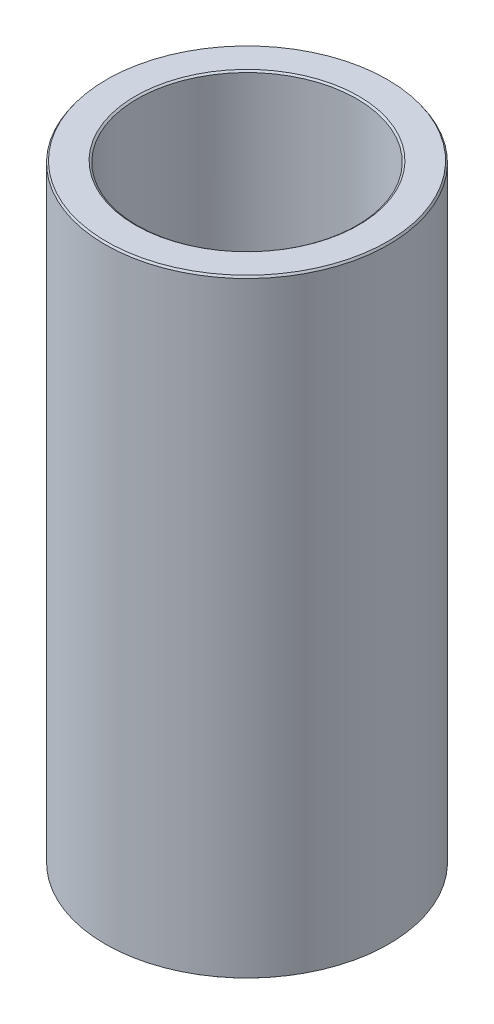
SolidWorks part; units mm, degrees
ref_plane "Front Plane" through (0, 0, 0) normal (0, 0, 1) x (1, 0, 0)
ref_plane "Top Plane" through (0, 0, 0) normal (0, 1, 0) x (1, 0, 0)
ref_plane "Right Plane" through (0, 0, 0) normal (1, 0, 0) x (0, 0, -1)
sketch "Sketch1" plane through (0, 0, 0) normal (0, 1, 0) x (1, 0, 0)
  circle A0 centre (0, 0) radius 35
  dimension "SLEEVE_OD" = 70
extrude "Boss-Extrude1" add sketch "Sketch1" along normal blind 150.343
sketch "Sketch2" plane through (0, 0, 0) normal (0, 1, 0) x (1, 0, 0)
  circle A0 centre (0, 0) radius 27.1021
  dimension "BORE_D" = 54.2042
extrude "Cut-Extrude1" cut sketch "Sketch2" along normal through all
chamfer "Chamfer1" distance 0.4712 angle 35.661 4 edges at (0, 150.343, 27.1021) (0, 0, 27.1021) (0, 0, 35) (0, 150.343, 35) first distance on face at (0, 150.343, 27.1021) first distance on face at (0, 0, 27.1021) first distance on face at (0, 150.343, 35)
